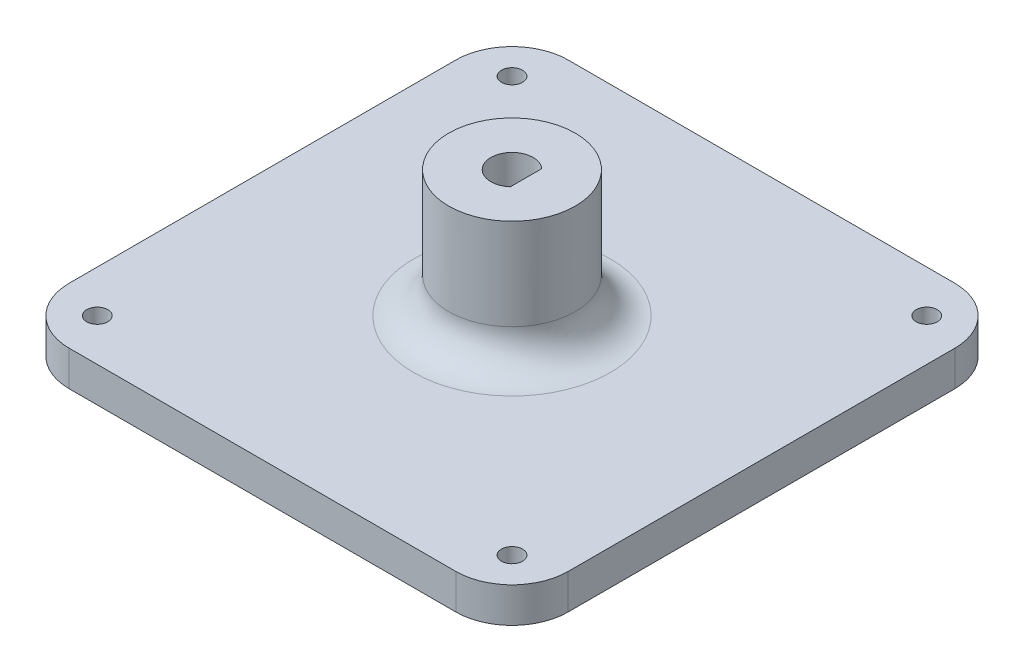
SolidWorks part; units mm, degrees
ref_plane "Front Plane" through (0, 0, 0) normal (0, 0, 1) x (1, 0, 0)
ref_plane "Top Plane" through (0, 0, 0) normal (0, 1, 0) x (1, 0, 0)
ref_plane "Right Plane" through (0, 0, 0) normal (1, 0, 0) x (0, 0, -1)
sketch "Sketch1" plane through (0, 0, 0) normal (0, 1, 0) x (1, 0, 0)
  line L1 (0, 0) -> (71, 0)
  line L2 (0, 0) -> (0, 71)
  line L3 (0, 71) -> (71, 71)
  line L4 (71, 0) -> (71, 71)
  dimension "D1" = 71
  dimension "D2" = 71
extrude "Boss-Extrude1" add sketch "Sketch1" along normal blind 5
sketch "Sketch2" plane through (0, 5, 0) normal (0, 1, 0) x (1, 0, 0)
  circle A0 centre (35.5, 35.5) radius 9
  point P0 (35.5, 35.5)
  dimension "D1" = 18
extrude "Boss-Extrude2" add sketch "Sketch2" along normal blind 18
fillet "Fillet1" radius 5 1 edges at (35.5, 5, -44.5)
sketch "Sketch3" plane through (0, 23, 0) normal (0, 1, 0) x (1, 0, 0)
  line L1 (37.5, 38.5) -> (40.6932, 38.5)
  line L2 (37.5, 38.5) -> (37.5, 32.5)
  line L3 (37.5, 32.5) -> (40.6932, 32.5)
  line L4 (40.6932, 38.5) -> (40.6932, 32.5)
  circle A0 centre (35.5, 35.5) radius 3
  point P0 (35.5, 35.5)
  dimension "D1" = 6
  dimension "D2" = 2
extrude "Cut-Extrude1" cut sketch "Sketch3" against normal blind 16 contours L2 A0 region at (35.204, 23, -35.5)
fillet "Fillet2" radius 8 4 edges at (0, 2.5, 0) (71, 2.5, 0) (71, 2.5, -71) (0, 2.5, -71)
sketch "Sketch4" plane through (0, 5, 0) normal (0, 1, 0) x (1, 0, 0)
  line L0 (63, 71) -> (8, 71) construction
  line L1 (71, 8) -> (71, 63) construction
  line L2 (8, 0) -> (63, 0) construction
  line L3 (0, 63) -> (0, 8) construction
  circle A0 centre (65, 65) radius 1.5
  circle A1 centre (65, 6) radius 1.5
  circle A2 centre (6, 6) radius 1.5
  circle A3 centre (6, 65) radius 1.5
  dimension "D1" = 3
  dimension "D6" = 3
  dimension "D9" = 3
  dimension "D12" = 3
  dimension "D2" = 6
  dimension "D3" = 6
  dimension "D4" = 6
  dimension "D5" = 6
  dimension "D7" = 6
  dimension "D8" = 6
  dimension "D10" = 6
  dimension "D11" = 6
extrude "Cut-Extrude2" cut sketch "Sketch4" against normal through all
sketch "Sketch5" plane through (0, 0, 0) normal (0, -1, 0) x (-1, 0, 0)
  line L1 (-43.6984, 35.5) -> (-39.5992, 28.4)
  line L2 (-39.5992, 28.4) -> (-31.4008, 28.4)
  line L3 (-31.4008, 28.4) -> (-27.3016, 35.5)
  line L4 (-27.3016, 35.5) -> (-31.4008, 42.6)
  line L5 (-31.4008, 42.6) -> (-39.5992, 42.6)
  line L6 (-39.5992, 42.6) -> (-43.6984, 35.5)
  circle A0 centre (-35.5, 35.5) radius 7.1 construction
  point P0 (-35.5, 35.5)
  dimension "D1" = 14.2
extrude "Cut-Extrude3" cut sketch "Sketch5" against normal blind 10
